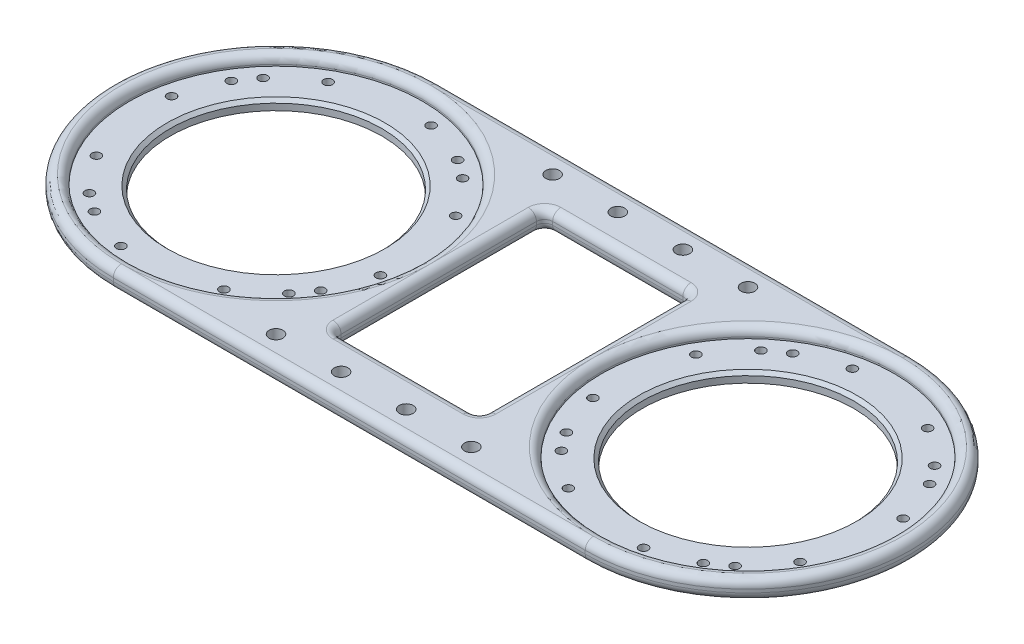
SolidWorks part; units mm, degrees
material "6061 合金"
ref_plane "前视基准面" through (0, 0, 0) normal (0, 0, 1) x (1, 0, 0)
ref_plane "上视基准面" through (0, 0, 0) normal (0, 1, 0) x (1, 0, 0)
ref_plane "右视基准面" through (0, 0, 0) normal (1, 0, 0) x (0, 0, -1)
other "Configuration Table"
sketch "草图1" plane through (0, 0, 0) normal (0, 1, 0) x (1, 0, 0)
  line L0 (-145, 0) -> (145, 0) construction
  line L1 (-145, 100) -> (145, 100)
  line L2 (-145, -100) -> (145, -100)
  arc A0 (-145, 100) -> (-145, -100) centre (-145, 0) ccw
  arc A1 (145, -100) -> (145, 100) centre (145, 0) ccw
  point P3 (0, 0)
  dimension "D1" = 100
  dimension "D2" = 290
extrude "凸台-拉伸1" add sketch "草图1" along normal blind 6 and the other way blind 6
sketch "草图2" plane through (0, 0, 0) normal (0, 0, 1) x (1, 0, 0)
  line L0 (-145, 6) -> (-145, -6) construction
  line L1 (-145, -6) -> (-80, -6)
  line L2 (-145, -6) -> (145, -6) construction
  line L3 (-80, -6) -> (-80, 0)
  line L4 (-80, 0) -> (-55, 0)
  line L5 (-55, 0) -> (-55, 6)
  line L6 (-145, 6) -> (145, 6) construction
  line L7 (-55, 6) -> (-145, 6)
  line L8 (-145, 6) -> (-145, -6)
  dimension "D1" = 130
  dimension "D2" = 180
revolve "切除-旋转1" cut sketch "草图2" angle 360 about L0
sketch "草图3" plane through (0, 0, 0) normal (0, 1, 0) x (1, 0, 0)
  line L0 (-145, 0) -> (-129.4354, 79.7452) construction
  line L1 (-73.8216, 39.1816) -> (-145, 0) construction
  line L2 (-102.9484, 69.5214) -> (-145, 0) construction
  line L3 (-91.648, 61.2791) -> (-145, 0) construction
  line L4 (-145, 0) -> (-145, 81.25) construction
  circle A0 centre (-145, 0) radius 81.25 construction
  circle A1 centre (-102.9484, 69.5214) radius 2.75
  circle A2 centre (-91.648, 61.2791) radius 2.75
  circle A3 centre (-73.8216, 39.1816) radius 2.75
  circle A4 centre (-129.4354, 79.7452) radius 2.75
  circle A5 centre (-145, 0) radius 65 construction
  circle A18 centre (-75.4786, -42.0516) radius 2.75
  circle A19 centre (-83.7209, -53.352) radius 2.75
  circle A20 centre (-105.8184, -71.1784) radius 2.75
  circle A21 centre (-65.2548, -15.5646) radius 2.75
  circle A22 centre (-187.0516, -69.5214) radius 2.75
  circle A23 centre (-198.352, -61.2791) radius 2.75
  circle A24 centre (-216.1784, -39.1816) radius 2.75
  circle A25 centre (-160.5646, -79.7452) radius 2.75
  circle A26 centre (-214.5214, 42.0516) radius 2.75
  circle A27 centre (-206.2791, 53.352) radius 2.75
  circle A28 centre (-184.1816, 71.1784) radius 2.75
  circle A29 centre (-224.7452, 15.5646) radius 2.75
  point P41 (-145, 0)
  dimension "D1" = 162.5
  dimension "D2" = 5.5
  dimension "D3" = 50.124
  dimension "D4" = 20.124
  dimension "D5" = 20.124
  dimension "D6" = 11.044
  dimension "D7" = 4
extrude "切除-拉伸1" cut sketch "草图3" against normal up to next
mirror "镜向1" about plane through (0, 0, 0) normal (1, 0, 0) of "切除-拉伸1", "切除-旋转1"
sketch "草图4" plane through (0, 6, 0) normal (0, 1, 0) x (1, 0, 0)
  line L0 (0, -80) -> (0, -100) construction
  line L1 (-145, -100) -> (145, -100) construction
  line L2 (-64, -100) -> (64, -100)
  arc A0 (0, -80) -> (64, -100) centre (64, 12.4) ccw
  arc A1 (0, -80) -> (-64, -100) centre (-64, 12.4) cw
  dimension "D1" = 20
  dimension "D2" = 64
extrude "切除-拉伸2" [suppressed] cut sketch "草图4" against normal up to next
fillet "圆角1" radius 5 4 edges at (0, -6, -100) (245, -6, 0) (0, -6, 100) (-245, -6, 0)
fillet "圆角2" radius 5 6 edges at (0, 6, -100) (245, 6, 0) (0, 6, 100) (-245, 6, 0) (-145, 6, 90) (145, 6, 90)
chamfer "倒角1" distance 2 angle 45 2 edges at (-145, 0, 65) (145, 0, 65)
sketch "草图5" [suppressed] plane through (0, 0, 0) normal (0, 0, 1) x (1, 0, 0)
  line L0 (-40, 6) -> (40, 6)
  line L1 (64, 6) -> (0, 6) construction
  line L2 (40, 6) -> (25, 86)
  line L3 (25, 86) -> (-25, 86)
  line L4 (0, 86) -> (0, 6) construction
  line L5 (-40, 6) -> (-25, 86)
  dimension "D1" = 80
  dimension "D2" = 50
  dimension "D3" = 80
extrude "凸台-拉伸2" [suppressed] add sketch "草图5" along normal mid plane 90
sketch "草图6" [suppressed] plane through (0, 0, 0) normal (1, 0, 0) x (0, 0, -1)
  line L0 (0, 86) -> (0, 6) construction
  line L1 (-45, 6) -> (45, 6) construction
  line L8 (-45, 86) -> (45, 86) construction
  line L16 (45, 6) -> (45, 86) construction
  line L17 (-39, 6) -> (39, 6)
  line L18 (-39, 6) -> (-39, 86)
  line L19 (-39, 86) -> (39, 86)
  line L20 (39, 6) -> (39, 86)
  line L21 (-39, 6) -> (39, 86) construction
  line L22 (-39, 86) -> (39, 6) construction
  point P5 (0, 6)
  point P6 (0, 46)
  dimension "D1" = 6
extrude "切除-拉伸3" [suppressed] cut sketch "草图6" against normal mid plane 150
sketch "草图7" [suppressed] plane through (0, 0, 0) normal (1, 0, 0) x (0, 0, -1)
  line L0 (-45, 6) -> (45, 6) construction
  line L1 (-45, 6) -> (45, 6) construction
  line L2 (45, 6) -> (95, 6) construction
  line L3 (70, 6) -> (45, 46)
  line L4 (45, 6) -> (45, 86) construction
rib "筋2" [suppressed] sketch "草图7" sketch "草图7" thickness 5 extrusion direction parallel to sketch draft on no parameters "D1"=5
sketch "草图8" [suppressed] plane through (0, 0, 0) normal (1, 0, 0) x (0, 0, -1)
  line L0 (-73.8482, 6) -> (-45, 6) construction
  line L1 (-73.8482, 6) -> (-45, 46)
  line L2 (-45, 6) -> (-45, 86) construction
rib "筋3" [suppressed] sketch "草图8" sketch "草图8" thickness 5 extrusion direction parallel to sketch draft on no parameters "D1"=5
sketch "草图9" [suppressed] plane through (0, 0, 45) normal (0, 0, 1) x (1, 0, 0)
  line L0 (25, 86) -> (-25, 86) construction
  line L1 (-17.5, 78) -> (17.5, 78) construction
  line L2 (-17.5, 78) -> (-17.5, 28) construction
  line L3 (-17.5, 28) -> (17.5, 28) construction
  line L4 (17.5, 78) -> (17.5, 28) construction
  line L5 (0, 86) -> (0, 6) construction
  circle A0 centre (-17.5, 78) radius 4.3
  circle A1 centre (17.5, 78) radius 4.3
  circle A2 centre (17.5, 28) radius 4.3
  circle A3 centre (-17.5, 28) radius 4.3
  point P9 (0, 78)
  dimension "D2" = 8.6
  dimension "D1" = 8
  dimension "D3" = 35
  dimension "D4" = 50
extrude "切除-拉伸4" [suppressed] cut sketch "草图9" against normal up to surface (90 mm away)
fillet "圆角4" [suppressed] radius 8
fillet "圆角5" [suppressed] radius 6
fillet "圆角6" [suppressed] radius 6
sketch "草图10" [suppressed] plane through (0, 6, 0) normal (0, 1, 0) x (1, 0, 0)
  line L0 (-45.08, 25) -> (45.08, 25)
  line L1 (46.6394, 31) -> (-46.6394, 31) construction
  line L2 (45.08, -25) -> (-45.08, -25)
  line L3 (-42, 0) -> (42, 0) construction
  arc A0 (45.08, 25) -> (45.08, -25) centre (145, 0) ccw
  arc A1 (-45.08, -25) -> (-45.08, 25) centre (-145, 0) ccw
  circle A2 centre (145, 0) radius 95 construction
  dimension "D1" = 8
  dimension "D2" = 6
extrude "切除-拉伸5" [suppressed] cut sketch "草图10" against normal up to next
fillet "圆角7" [suppressed] radius 5
sketch "草图11" plane through (0, 6, 0) normal (0, 1, 0) x (1, 0, 0)
  line L0 (-275.0843, 0) -> (287.0305, 0) construction
  line L1 (0, 0) -> (0, 187.1026) construction
  line L2 (-45, 65) -> (45, 65)
  line L3 (-45, 65) -> (-45, -65)
  line L4 (-45, -65) -> (45, -65)
  line L5 (45, 65) -> (45, -65)
  dimension "D1" = 90
  dimension "D2" = 130
extrude "切除-拉伸6" cut sketch "草图11" against normal blind 47
fillet "圆角8" radius 5 12 edges at (-45, -6, 0) (0, -6, 65) (0, -6, -65) (45, -6, 0) (45, 0, -65) (-45, 0, -65) (45, 0, 65) (-45, 0, 65) (0, 6, 65) (45, 6, 0) (-45, 6, 0) (0, 6, -65)
sketch "草图12" plane through (0, 6, 0) normal (0, 1, 0) x (1, 0, 0)
  line L0 (-265.7211, 0) -> (250.8692, 0) construction
  line L1 (0, 152.8784) -> (0, -181.2909) construction
  circle A1 centre (60, -85) radius 4.25
  circle A2 centre (20, -85) radius 4.25
  circle A3 centre (-20, -85) radius 4.25
  circle A4 centre (-60, -85) radius 4.25
  circle A5 centre (20, 85) radius 4.25
  circle A6 centre (60, 85) radius 4.25
  circle A7 centre (-60, 85) radius 4.25
  circle A8 centre (-20, 85) radius 4.25
  dimension "D1" = 8.5
  dimension "D2" = 85
  dimension "D3" = 20
  dimension "D4" = 40
extrude "切除-拉伸7" cut sketch "草图12" against normal blind 47
